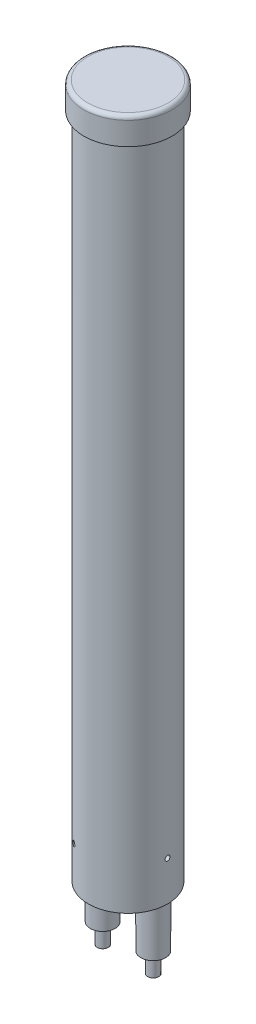
SolidWorks part; units mm, degrees
material "ABS"
ref_plane "Płaszczyzna przednia" through (0, 0, 0) normal (0, 0, 1) x (1, 0, 0)
ref_plane "Płaszczyzna górna" through (0, 0, 0) normal (0, 1, 0) x (1, 0, 0)
ref_plane "Płaszczyzna prawa" through (0, 0, 0) normal (1, 0, 0) x (0, 0, -1)
sketch "Sketch1" plane through (0, 0, 0) normal (0, 1, 0) x (1, 0, 0)
  circle A0 centre (0, 0) radius 20
  dimension "D1" = 40
extrude "Boss-Extrude1" add sketch "Sketch1" along normal blind 345
sketch "Sketch2" plane through (0, 345, 0) normal (0, 1, 0) x (1, 0, 0)
  circle A0 centre (0, 0) radius 22.25
  dimension "D1" = 44.5
extrude "Boss-Extrude2" add sketch "Sketch2" along normal blind 5 and the other way blind 8.5
fillet "Fillet1" radius 2 1 edges at (0, 350, 22.25)
ref_plane "Plane1" through (20, 0, 0) normal (1, 0, 0) x (0, 0, -1)
sketch "Sketch3" plane through (20, 0, 0) normal (1, 0, 0) x (0, 0, -1)
  line L0 (0, 0) -> (0, 20) construction
  circle A0 centre (0, 20) radius 1.25
  dimension "D2" = 2.5
  dimension "D1" = 20
extrude "Cut-Extrude1" cut sketch "Sketch3" against normal blind 5
pattern_circular "CirPattern1" count 3 every 120 about axis through (0, 345, 0) along (0, -1, 0) of "Cut-Extrude1" reverse direction yes
sketch "Sketch4" plane through (0, 0, 0) normal (0, -1, 0) x (1, 0, 0)
  line L0 (12.75, 0) -> (0, 0) construction
  line L1 (0, 0) -> (-12.75, 0) construction
  circle A0 centre (-12.75, 0) radius 6.25
  circle A1 centre (12.75, 0) radius 6.25
  dimension "D1" = 25.5
  dimension "D2" = 12.5
extrude "Boss-Extrude3" add sketch "Sketch4" along normal blind 24
sketch "Sketch5" plane through (0, -24, 0) normal (0, -1, 0) x (1, 0, 0)
  circle A0 centre (-12.75, 0) radius 2.8
  circle A1 centre (12.75, 0) radius 2.8
  dimension "D1" = 5.6
extrude "Boss-Extrude4" add sketch "Sketch5" along normal blind 10
